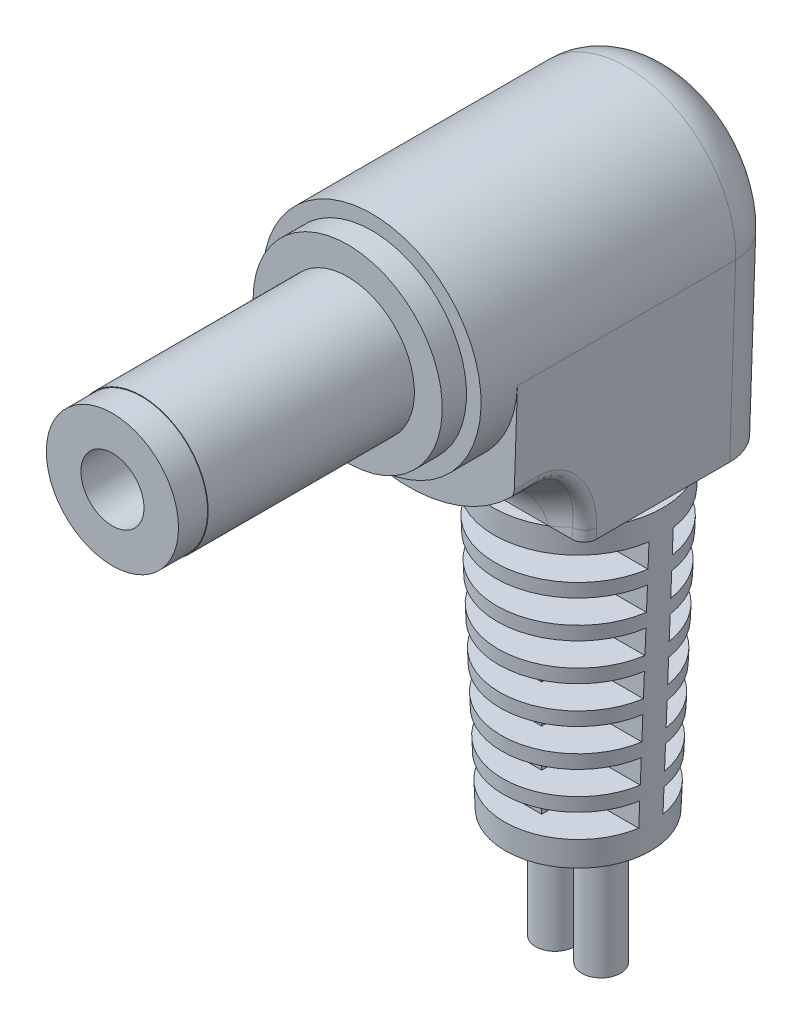
SolidWorks part; units mm, degrees
ref_plane "前视基准面" through (0, 0, 0) normal (0, 0, 1) x (1, 0, 0)
ref_plane "上视基准面" through (0, 0, 0) normal (0, 1, 0) x (1, 0, 0)
ref_plane "右视基准面" through (0, 0, 0) normal (1, 0, 0) x (0, 0, -1)
sketch "草图1" plane through (0, 0, 0) normal (0, 0, 1) x (1, 0, 0)
  circle A0 centre (0, 0) radius 2.725
  circle A1 centre (0, 0) radius 1.3
  dimension "D1" = 2.6
  dimension "D2" = 5.45
extrude "凸台-拉伸1" add sketch "草图1" along normal blind 1.2
sketch "草图2" plane through (0, 0, 0) normal (0, 0, -1) x (-1, 0, 0)
  circle A0 centre (0, 0) radius 2.75
  circle A1 centre (0, 0) radius 1.3
extrude "凸台-拉伸2" add sketch "草图2" along normal blind 8.5
sketch "草图3" plane through (0, 0, -8.5) normal (0, 0, -1) x (-1, 0, 0)
  circle A0 centre (0, 0) radius 3.9
extrude "凸台-拉伸3" add sketch "草图3" along normal blind 1
sketch "草图4" plane through (0, 0, -9.5) normal (0, 0, -1) x (-1, 0, 0)
  circle A0 centre (0, 0) radius 4.5
extrude "凸台-拉伸4" add sketch "草图4" along normal blind 1.5
sketch "草图5" plane through (0, 0, -11) normal (0, 0, -1) x (-1, 0, 0)
  line L0 (-4.3635, -4.1182) -> (-4.4974, -0.1518)
  line L2 (4.3635, -4.1182) -> (4.4974, -0.1518)
  line L3 (0, 0) -> (0, -11.9616) construction
  arc A0 (4.4974, -0.1518) -> (-4.4974, -0.1518) centre (0, 0) ccw
  arc A1 (-4.3635, -4.1182) -> (4.3635, -4.1182) centre (0, 0) ccw
  dimension "D2" = 9
extrude "凸台-拉伸5" add sketch "草图5" along normal blind 3
sketch "草图6" plane through (0, 0, -14) normal (0, 0, -1) x (-1, 0, 0)
  line L0 (0, 0) -> (0, -11.1557) construction
  line L1 (-4.2494, -7.5) -> (4.2494, -7.5)
  line L2 (-4.3635, -4.1182) -> (-4.1187, -11.3701) construction
  line L3 (4.4305, -2.135) -> (4.1187, -11.3701) construction
  line L4 (4.3635, -4.1182) -> (4.4974, -0.1518) construction
  line L5 (4.1187, -11.3701) -> (-4.1187, -11.3701) construction
  line L6 (-4.4974, -0.1518) -> (-4.3635, -4.1182) construction
  line L7 (-4.2494, -7.5) -> (-4.4974, -0.1518)
  line L8 (4.4974, -0.1518) -> (4.2494, -7.5)
  arc A0 (4.4974, -0.1518) -> (-4.4974, -0.1518) centre (0, 0) ccw
  dimension "D1" = 7.5
extrude "凸台-拉伸6" add sketch "草图6" along normal blind 8
fillet "圆角2" radius 2 3 edges at (-4.3734, -3.8259, -22) (4.3734, -3.8259, -22) (0, 4.5, -22)
fillet "圆角3" radius 2 1 edges
fillet "圆角4" radius 0.5 6 edges at (-4.3387, -4.8549, -13.3353) (4.351, -4.4881, -12.97)
sketch "草图7" plane through (0, -7.5, 0) normal (0, -1, 0) x (1, 0, 0)
  line L0 (2.7839, -14) -> (-2.7839, -14) construction
  circle A0 centre (0, -18) radius 3
  dimension "D2" = 6
  dimension "D1" = 4
extrude "凸台-拉伸7" add sketch "草图7" along normal blind 1
sketch "草图8" plane through (0, 0, 0) normal (1, 0, 0) x (0, 0, -1)
  line L0 (18, -8.5) -> (18, -21) construction
  line L1 (15, -8.5) -> (21, -8.5) construction
  line L2 (18, -8.5) -> (14.5, -8.5)
  line L3 (14.5, -8.5) -> (15, -21)
  line L4 (15, -21) -> (18, -21)
  line L5 (18, -21) -> (18, -8.5)
  dimension "D1" = 3.5
  dimension "D2" = 3
  dimension "D3" = 12.5
revolve "旋转1" add sketch "草图8" angle 360 about L0
sketch "草图9" plane through (0, 0, 0) normal (1, 0, 0) x (0, 0, -1)
  line L0 (18, -7.5) -> (18, -23.7149) construction
  line L1 (15, -7.5) -> (21, -7.5) construction
  line L2 (21.5, -8.5) -> (14.5, -8.5) construction
  line L3 (9.8817, -10.5) -> (17.5, -10.5)
  line L4 (9.8817, -10.5) -> (9.8817, -9.5)
  line L5 (9.8817, -9.5) -> (17.5, -9.5)
  line L6 (17.5, -10.5) -> (17.5, -9.5)
  line L8 (18.5, -9.5) -> (23.7602, -9.5)
  line L9 (18.5, -9.5) -> (18.5, -10.5)
  line L10 (18.5, -10.5) -> (23.7602, -10.5)
  line L11 (23.7602, -9.5) -> (23.7602, -10.5)
  dimension "D1" = 1
  dimension "D2" = 7.6183
  dimension "D3" = 1
  dimension "D4" = 0.5
  dimension "D5" = 0.5
  dimension "D6" = 1
  dimension "D7" = 1
extrude "切除-拉伸1" cut sketch "草图9" against normal mid plane 8
pattern_linear "阵列(线性)1" count 7 spacing 1.575 along (-0.0337, -0.9994, 0) of "切除-拉伸1"
sketch "草图10" plane through (0, -21, 0) normal (0, -1, 0) x (1, 0, 0)
  line L0 (2.7839, -14) -> (-2.7839, -14) construction
  circle A0 centre (-0.95, -18) radius 0.8
  circle A1 centre (0.95, -18) radius 0.8
  circle A2 centre (0, -18) radius 3 construction
  point P2 (0, -14)
  dimension "D1" = 0.95
  dimension "D2" = 1.6
  dimension "D3" = 1.6
  dimension "D4" = 0.95
extrude "凸台-拉伸8" add sketch "草图10" against normal up to surface (11.5 mm away) up to face at (0, -9.5, -16.02)
sketch "草图11" plane through (0, -21, 0) normal (0, -1, 0) x (1, 0, 0)
  circle A0 centre (-0.95, -18) radius 0.8
  circle A1 centre (0.95, -18) radius 0.8
extrude "凸台-拉伸9" add sketch "草图11" along normal blind 5
sketch "草图12" plane through (0, -21, 0) normal (0, -1, 0) x (1, 0, 0)
  line L0 (0, -14) -> (0, -21.1452) construction
  line L1 (2.7839, -14) -> (-2.7839, -14) construction
  line L3 (-0.5, -16) -> (0.5, -16)
  line L4 (-0.5, -16) -> (-0.5, -20)
  line L5 (-0.5, -20) -> (0.5, -20)
  line L6 (0.5, -16) -> (0.5, -20)
  arc A0 (-3.1052, -18.5) -> (3.1052, -18.5) centre (0, -18) ccw construction
  circle A1 centre (0, -18) radius 3 construction
  dimension "D1" = 1
  dimension "D2" = 0.5
  dimension "D3" = 4
  dimension "D4" = 2
extrude "凸台-拉伸10" add sketch "草图12" against normal up to surface (11.5 mm away) up to face at (0, -9.5, -16.9067)
